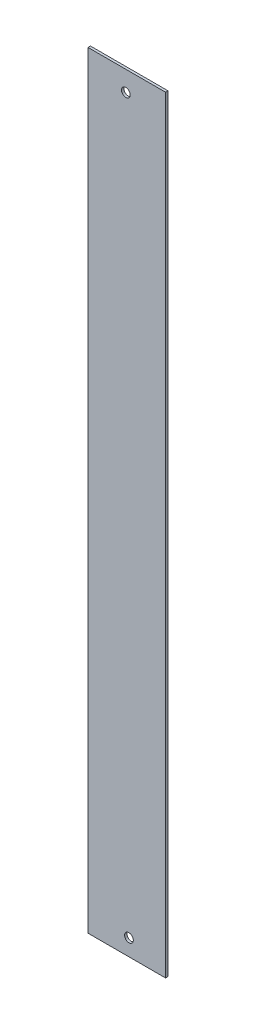
SolidWorks part; units mm, degrees
ref_plane "Front Plane" through (0, 0, 0) normal (0, 0, 1) x (1, 0, 0)
ref_plane "Top Plane" through (0, 0, 0) normal (0, 1, 0) x (1, 0, 0)
ref_plane "Right Plane" through (0, 0, 0) normal (1, 0, 0) x (0, 0, -1)
sketch "Sketch1" plane through (0, 0, 0) normal (0, 0, 1) x (1, 0, 0)
  line L1 (0, 0) -> (44.5, 0)
  line L2 (0, 0) -> (0, 440)
  line L3 (0, 440) -> (44.5, 440)
  line L4 (44.5, 0) -> (44.5, 440)
  line L5 (0, 0) -> (44.5, 440) construction
  line L6 (0, 440) -> (44.5, 0) construction
  point P4 (22.25, 220)
  dimension "D1" = 440
  dimension "D2" = 44.5
base flange "Base-Flange1" sketch "Sketch1" thickness 1.4 reverse thickness direction no parameters "D1"=2
sketch "Sketch6" plane through (0, 0, 0) normal (0, 0, 1) x (1, 0, 0)
  line L0 (44.5, 440) -> (0, 440) construction
  line L1 (0, 0) -> (44.5, 0) construction
  line L2 (44.5, 0) -> (44.5, 440) construction
  circle A0 centre (21.7, 428.5) radius 2.5
  circle A1 centre (23.5, 9.5) radius 2.5
  dimension "D1" = 5
  dimension "D2" = 5
  dimension "D3" = 11.5
  dimension "D4" = 9.5
  dimension "D5" = 21
  dimension "D6" = 22.8
extrude "Cut-Extrude1" cut sketch "Sketch6" against normal up to next normal cut yes
sketch "Bend-Lines1" [suppressed] plane through (0, 0, 0) normal (0, 1, 0) x (1, 0, 0)
sketch "Bounding-Box1" [suppressed] plane through (0, 0, 0) normal (0, 1, 0) x (1, 0, 0)
sheet metal parameters "Sheet-Metal1" thickness 1.4 parameters "D1"=2
flat pattern "Flat-Pattern1" [suppressed]
sketch "Bend-Lines2" plane through (0, 0, 0) normal (0, 1, 0) x (1, 0, 0)
sketch3d "Bounding-Box2" [suppressed]
  line L0 (-44.5, 476, 0) -> (-44.5, 0, 0) construction
  line L1 (0, 476, 0) -> (0, 0, 0) construction
  line L2 (-44.5, 476, 0) -> (0, 476, 0) construction
  line L3 (-44.5, 0, 0) -> (0, 0, 0) construction
sheet metal parameters "Sheet-Metal2" thickness 1.4 parameters "D1"=2
flat pattern "Flat-Pattern1"
sketch "Bend-Lines2" plane through (0, 0, 0) normal (0, 1, 0) x (1, 0, 0)
sketch3d "Bounding-Box2" [suppressed]
  line L0 (44.5, 440, 0) -> (44.5, 0, 0) construction
  line L1 (0, 440, 0) -> (0, 0, 0) construction
  line L2 (44.5, 440, 0) -> (0, 440, 0) construction
  line L3 (44.5, 0, 0) -> (0, 0, 0) construction
